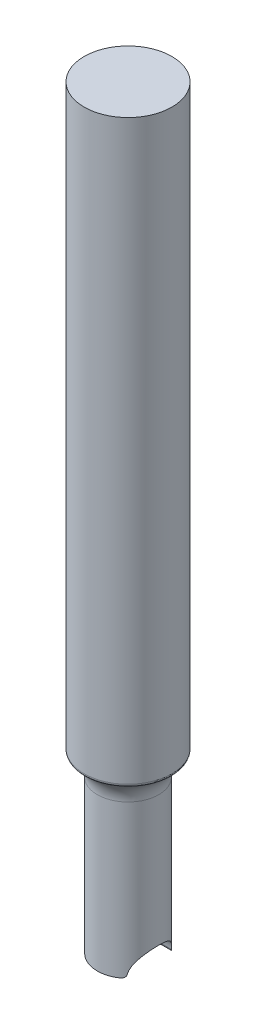
SolidWorks part; units mm, degrees
ref_plane "Front Plane" through (0, 0, 0) normal (0, 0, 1) x (1, 0, 0)
ref_plane "Top Plane" through (0, 0, 0) normal (0, 1, 0) x (1, 0, 0)
ref_plane "Right Plane" through (0, 0, 0) normal (1, 0, 0) x (0, 0, -1)
sketch "Sketch1" plane through (0, 0, 0) normal (0, 1, 0) x (1, 0, 0)
  circle A0 centre (0, 0) radius 6.35
  dimension "D1" = 12.7
extrude "Boss-Extrude1" add sketch "Sketch1" along normal blind 83.82
sketch "Sketch3" plane through (0, 0, 0) normal (0, 1, 0) x (1, 0, 0)
  circle A0 centre (0, 0) radius 4.445
  dimension "D1" = 8.89
extrude "Boss-Extrude2" add sketch "Sketch3" against normal blind 25.4
fillet "Fillet1" radius 3.81 1 edges at (0, 0, 4.445)
sketch "Sketch4" plane through (0, 0, 0) normal (1, 0, 0) x (0, 0, -1)
  line L0 (-4.445, -25.4) -> (4.445, -25.4) construction
  circle A0 centre (0, -25.4) radius 3.2385
  dimension "D1" = 6.477
extrude "Cut-Extrude1" cut sketch "Sketch4" along normal blind 7.62 and the other way blind 7.62
fillet "Fillet2" radius 0.508 3 edges at (0, -25.4, -3.2385) (0, -25.4, 3.2385) (0, 0, 6.35)
